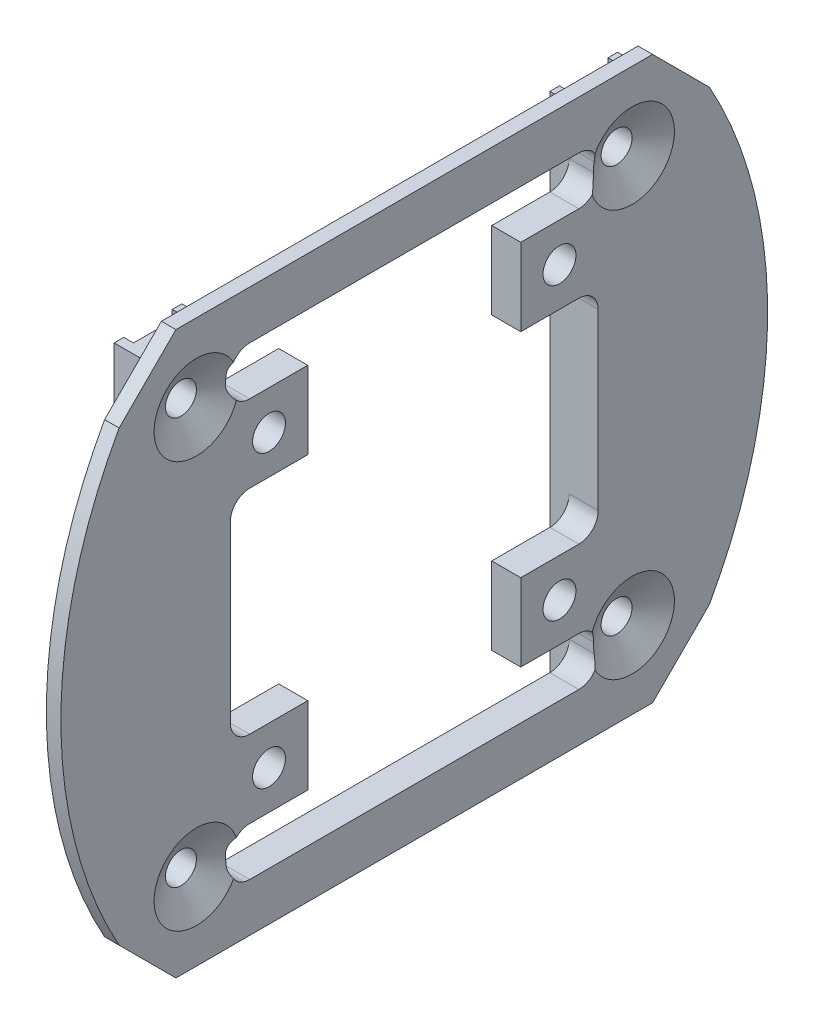
SolidWorks part; units mm, degrees
ref_plane "前视基准面" through (0, 0, 0) normal (0, 0, 1) x (1, 0, 0)
ref_plane "上视基准面" through (0, 0, 0) normal (0, 1, 0) x (1, 0, 0)
ref_plane "右视基准面" through (0, 0, 0) normal (1, 0, 0) x (0, 0, -1)
sketch "草图1" plane through (0, 0, 0) normal (1, 0, 0) x (0, 0, -1)
  line L0 (0, 36.1871) -> (0, -43.9928) construction
  line L1 (-29, -29) -> (29, -29)
  line L2 (-29, -29) -> (-29, 29)
  line L3 (-29, 29) -> (29, 29)
  line L4 (29, -29) -> (29, 29)
  line L5 (-29, -29) -> (29, 29) construction
  line L6 (-29, 29) -> (29, -29) construction
  line L7 (-46.4663, 0) -> (41.6425, 0) construction
  line L8 (-17, 24) -> (17, 24)
  line L9 (19, 22) -> (19, 21)
  line L10 (17, 19) -> (11, 19)
  line L11 (11, 19) -> (11, 11)
  line L12 (11, 11) -> (17, 11)
  line L13 (19, -9) -> (19, 9)
  line L14 (-19, 22) -> (-19, 21)
  line L15 (-17, 19) -> (-11, 19)
  line L16 (-11, 19) -> (-11, 11)
  line L17 (-11, 11) -> (-17, 11)
  line L18 (-19, -9) -> (-19, 9)
  line L19 (11, -11) -> (17, -11)
  line L20 (11, -19) -> (11, -11)
  line L21 (17, -19) -> (11, -19)
  line L22 (19, -22) -> (19, -21)
  line L23 (-17, -24) -> (17, -24)
  line L24 (-19, -22) -> (-19, -21)
  line L25 (-17, -19) -> (-11, -19)
  line L26 (-11, -19) -> (-11, -11)
  line L27 (-11, -11) -> (-17, -11)
  arc A0 (19, 9) -> (17, 11) centre (17, 9) ccw
  arc A1 (17, 19) -> (19, 21) centre (17, 21) ccw
  arc A2 (19, 22) -> (17, 24) centre (17, 22) ccw
  arc A3 (-19, 22) -> (-17, 24) centre (-17, 22) cw
  arc A4 (-17, 19) -> (-19, 21) centre (-17, 21) cw
  arc A5 (-19, 9) -> (-17, 11) centre (-17, 9) cw
  arc A6 (19, -9) -> (17, -11) centre (17, -9) cw
  arc A7 (17, -19) -> (19, -21) centre (17, -21) cw
  arc A8 (19, -22) -> (17, -24) centre (17, -22) cw
  arc A9 (-19, -22) -> (-17, -24) centre (-17, -22) ccw
  arc A10 (-17, -19) -> (-19, -21) centre (-17, -21) ccw
  arc A11 (-19, -9) -> (-17, -11) centre (-17, -9) ccw
  circle A12 centre (15, 15) radius 1.7
  circle A13 centre (-15, 15) radius 1.7
  circle A14 centre (-15, -15) radius 1.7
  circle A15 centre (15, -15) radius 1.7
  point P0 (0, 0)
  point P21 (19, 19)
  point P24 (19, 24)
  point P26 (0, 24)
  point P38 (19, 0)
  point P59 (-19, 0)
  dimension "D7" = 2
  dimension "D9" = 3.4
  dimension "D12" = 38
  dimension "D1" = 58
  dimension "D2" = 58
  dimension "D3" = 24
  dimension "D4" = 19
  dimension "D5" = 8
  dimension "D6" = 8
  dimension "D8" = 22
  dimension "D10" = 15
  dimension "D11" = 15
  dimension "D13" = 48
  dimension "D14" = 30
  dimension "D15" = 38
  dimension "D16" = 22
extrude "凸台-拉伸1" add sketch "草图1" along normal blind 5
sketch "草图2" plane through (0, 0, 0) normal (-1, 0, 0) x (0, 0, 1)
  line L1 (-29, -29) -> (29, -29)
  line L2 (-29, -29) -> (-29, 29)
  line L3 (-29, 29) -> (29, 29)
  line L4 (29, -29) -> (29, 29)
  line L5 (-29, -29) -> (29, 29) construction
  line L6 (-29, 29) -> (29, -29) construction
  line L7 (-26, -26) -> (26, -26)
  line L8 (-26, -26) -> (-26, 26)
  line L9 (-26, 26) -> (26, 26)
  line L10 (26, -26) -> (26, 26)
  line L11 (-26, -26) -> (26, 26) construction
  line L12 (-26, 26) -> (26, -26) construction
  point P0 (0, 0)
  point P7 (0, 0)
  dimension "D1" = 52
extrude "切除-拉伸1" cut sketch "草图2" against normal blind 3.5
sketch "草图3" plane through (0, 0, 0) normal (-1, 0, 0) x (0, 0, 1)
  line L0 (26, 26) -> (-26, 26) construction
  line L1 (-19, -26) -> (19, -26)
  line L2 (-19, -26) -> (-19, 26)
  line L3 (-19, 26) -> (19, 26)
  line L4 (19, -26) -> (19, 26)
  line L5 (-19, -26) -> (19, 26) construction
  line L6 (-19, 26) -> (19, -26) construction
  point P1 (0, 0)
  dimension "D1" = 38
extrude "切除-拉伸2" cut sketch "草图3" against normal blind 2
sketch "草图4" plane through (0, 0, 0) normal (-1, 0, 0) x (0, 0, 1)
  line L0 (-22.5, 26) -> (-22.5, -26) construction
  line L1 (-19, 26) -> (-26, 26) construction
  line L2 (-26, -26) -> (-19, -26) construction
  line L3 (22.5, 26) -> (22.5, -26) construction
  line L6 (26, 26) -> (19, 26) construction
  line L7 (-26, -26) -> (26, -26) construction
  line L9 (-25, -26) -> (-20, -26)
  line L10 (-25, -26) -> (-25, 26)
  line L11 (-25, 26) -> (-20, 26)
  line L12 (-20, -26) -> (-20, 26)
  line L13 (-25, -26) -> (-20, 26) construction
  line L14 (-25, 26) -> (-20, -26) construction
  line L15 (20, -26) -> (25, -26)
  line L16 (20, -26) -> (20, 26)
  line L17 (20, 26) -> (25, 26)
  line L18 (25, -26) -> (25, 26)
  line L19 (20, -26) -> (25, 26) construction
  line L20 (20, 26) -> (25, -26) construction
  point P12 (-22.5, 0)
  point P17 (22.5, 0)
  dimension "D1" = 5
  dimension "D2" = 5
extrude "切除-拉伸3" cut sketch "草图4" against normal blind 1
ref_plane "基准面1" through (0, 0, 22.5) normal (0, 0, 1) x (1, 0, 0)
ref_plane "基准面2" through (0, 21, 0) normal (0, 1, 0) x (1, 0, 0)
ref_axis "基准轴1" through (0.4829, 21, 22.5) along (1, 0, 0)
sketch "草图7" plane through (0, 0, 22.5) normal (0, 0, 1) x (1, 0, 0)
  line L0 (3.4173, 21) -> (7.484, 21) construction
  line L1 (0.825, 21) -> (-0.825, 21) construction
sketch "草图8" plane through (1, 0, 0) normal (-1, 0, 0) x (0, 0, 1)
  circle A0 centre (22.5, 21) radius 1.6
  dimension "D1" = 3.2
extrude "切除-拉伸4" cut sketch "草图8" against normal blind 2.4
sketch "草图9" plane through (0, 0, 22.5) normal (0, 0, 1) x (1, 0, 0)
  line L0 (3.4, 19.4) -> (3.4, 21)
  line L1 (3.4, 22.6) -> (3.4, 19.4) construction
  line L2 (3.4, 19.4) -> (5, 16.6287)
  line L3 (5, 19) -> (5, 11) construction
  line L4 (5, 16.6287) -> (5, 21)
  line L5 (3.4173, 21) -> (7.484, 21) construction
  line L6 (3.4, 21) -> (5, 21)
  dimension "D2" = 60
revolve "切除-旋转2" cut sketch "草图9" angle 360 about L0
pattern_linear "阵列(线性)1" count 2 spacing 45 along (0, 0, -1) count 2 spacing 42 along (0, -1, 0) of "切除-拉伸4", "切除-旋转2"
sketch "草图10" plane through (5, 0, 0) normal (1, 0, 0) x (0, 0, -1)
  line L0 (-16, 29) -> (-16, -29) construction
  line L1 (29, 29) -> (-29, 29) construction
  line L2 (-29, -29) -> (29, -29) construction
  line L5 (-29, 25.6174) -> (-29, -25.6174)
  line L6 (29, 25.6174) -> (29, -25.6174)
  arc A0 (29, -25.6174) -> (29, 25.6174) centre (-11, 0) ccw
  arc A1 (-29, -25.6174) -> (-29, 25.6174) centre (11, 0) cw
  dimension "D2" = 95
  dimension "D1" = 45
extrude "凸台-拉伸2" add sketch "草图10" against normal blind 1.5
sketch "草图12" plane through (5, 0, 0) normal (1, 0, 0) x (0, 0, -1)
  arc A0 (0, -46.2088) -> (0, 46.2088) centre (-11, 0) ccw
  arc A1 (0, 46.2088) -> (0, -46.2088) centre (11, 0) ccw
  circle A2 centre (0, 0) radius 63.0049
extrude "切除-拉伸6" cut sketch "草图12" against normal blind 1.5
chamfer "倒角2" distance 2 angle 45 1 edges at (4.25, 29, 26.6198) first distance on face at (4.25, 29, 0)
chamfer "倒角3" distance 2 angle 45 1 edges at (4.25, 29, -26.6198) first distance on face at (4.25, 29, -1)
chamfer "倒角5" distance 2 angle 45 1 edges at (4.25, -29, -26.6198) first distance on face at (4.25, -29, 0)
chamfer "倒角6" distance 2 angle 45 1 edges at (4.25, -29, 26.6198) first distance on face at (4.25, -29, 1)
